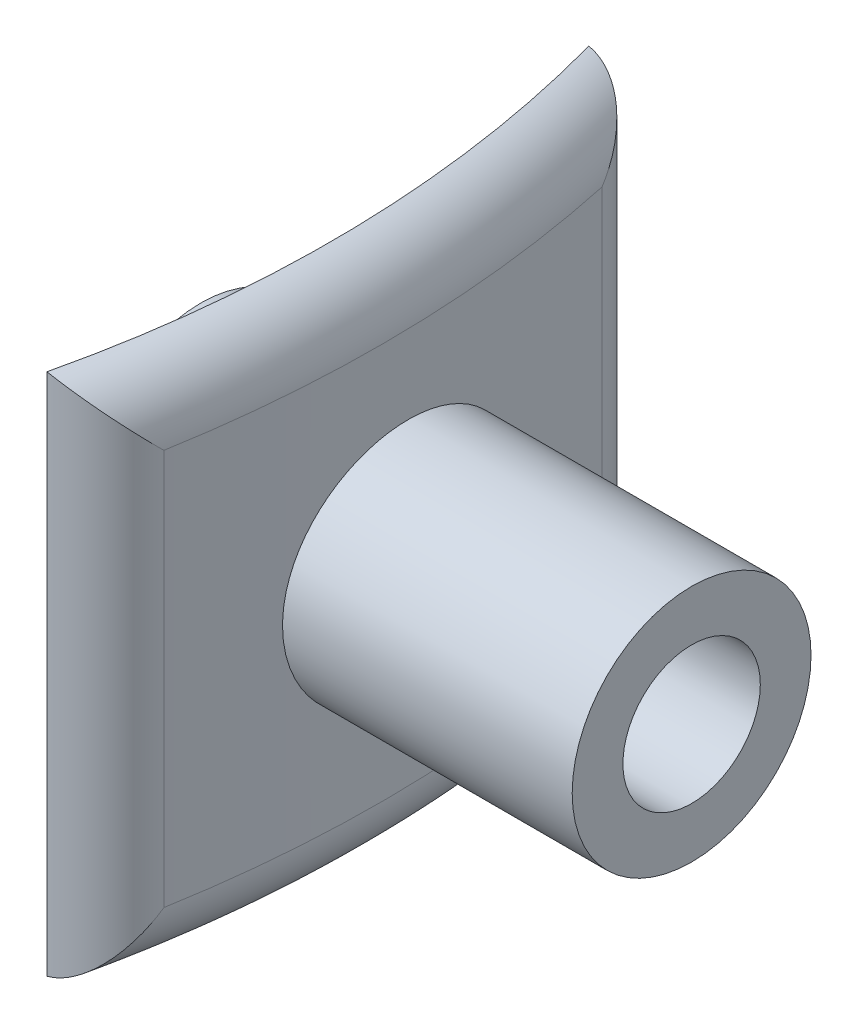
SolidWorks part; units mm, degrees
ref_plane "Front Plane" through (0, 0, 0) normal (0, 0, 1) x (1, 0, 0)
ref_plane "Top Plane" through (0, 0, 0) normal (0, 1, 0) x (1, 0, 0)
ref_plane "Right Plane" through (0, 0, 0) normal (1, 0, 0) x (0, 0, -1)
sketch "Sketch3" plane through (0, 0, 0) normal (1, 0, 0) x (0, 0, -1)
  circle A0 centre (0, 0) radius 3.65
  circle A1 centre (0, 0) radius 2.1
  dimension "D1" = 7.3
  dimension "D2" = 4.2
extrude "Boss-Extrude3" add sketch "Sketch3" along normal blind 15 contours A1 | A0 region at (0, 0, 0)
sketch "Sketch6" plane through (0, 0, 0) normal (0, 1, 0) x (1, 0, 0)
  line L1 (3.4775, 8.3808) -> (4.92, 8.9783)
  line L2 (3.8195, -8.5225) -> (5.27, -9.1233)
  arc A0 (3.8195, -8.5225) -> (3.4775, 8.3808) centre (-29.5351, -0.7421) ccw
  arc A1 (5.27, -9.1233) -> (4.92, 8.9783) centre (-29.5351, -0.7421) ccw
  circle A2 centre (-29.5351, -0.7421) radius 34.25 construction
  circle A3 centre (-29.5351, -0.7421) radius 35.8 construction
  dimension "D1" = 1.55
extrude "Boss-Extrude4" add sketch "Sketch6" along normal blind 8 and the other way blind 8 contours L2 A1 L1 A0
sketch "Sketch7" plane through (0, 0, 0) normal (-1, 0, 0) x (0, 0, 1)
  circle A0 centre (0, 0) radius 2.1
extrude "Cut-Extrude1" cut sketch "Sketch7" against normal blind 18
fillet "Fillet2" radius 2 4 edges at (6.2582, 8, 0.05) (4.92, 0, -8.9783) (6.2582, -8, 0.05) (5.27, 0, 9.1233)
